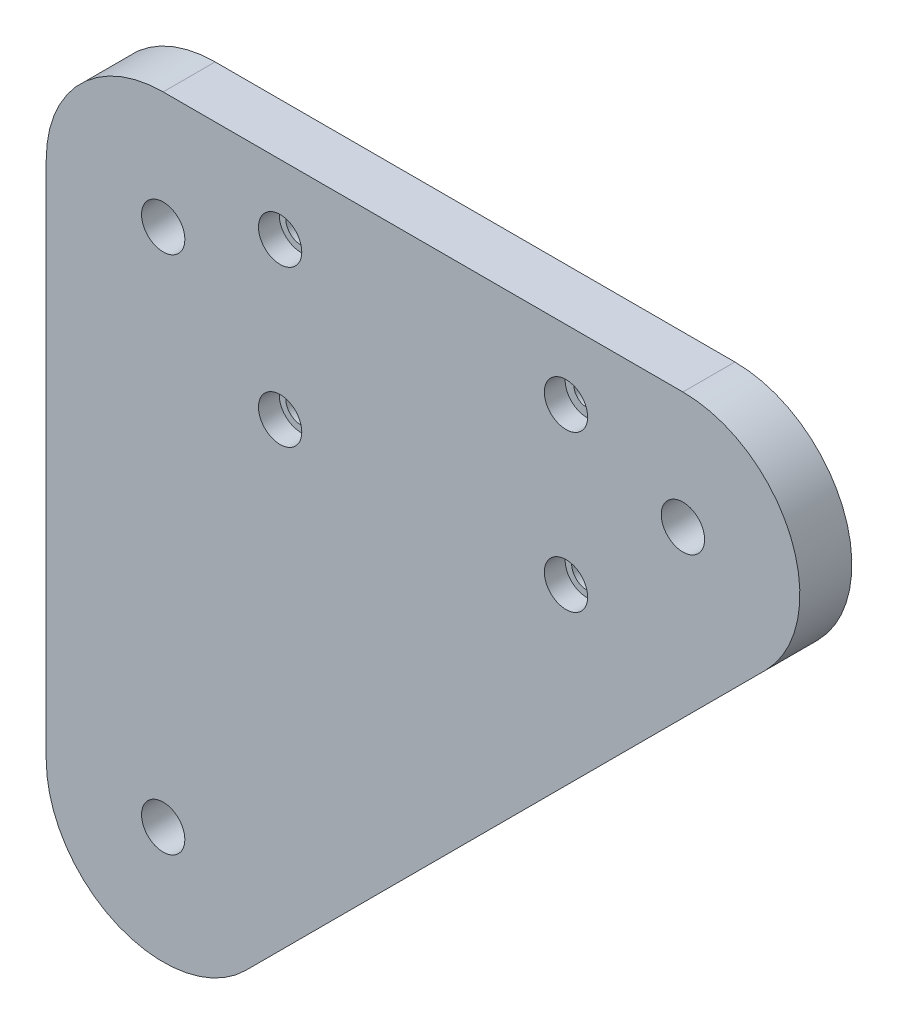
SolidWorks part; units mm, degrees
ref_plane "Plano frontal" through (0, 0, 0) normal (0, 0, 1) x (1, 0, 0)
ref_plane "Plano superior" through (0, 0, 0) normal (0, 1, 0) x (1, 0, 0)
ref_plane "Plano direito" through (0, 0, 0) normal (1, 0, 0) x (0, 0, -1)
sketch "Esboço1" plane through (0, 0, 0) normal (0, 0, 1) x (1, 0, 0)
  line L1 (-30, 30) -> (30, 30) construction
  line L2 (-30, 30) -> (-30, -30) construction
  line L3 (-30, -30) -> (30, -30) construction
  line L4 (30, 30) -> (30, -30) construction
  line L5 (-30, 30) -> (30, -30) construction
  line L6 (-30, -30) -> (30, 30) construction
  line L8 (30, 43.5) -> (-30, 43.5)
  line L23 (-20.4541, -39.5459) -> (39.5459, 20.4541)
  line L26 (-43.5, -30) -> (-43.5, 30)
  circle A0 centre (-30, 30) radius 2.5
  circle A1 centre (-30, -30) radius 2.5
  circle A2 centre (30, 30) radius 2.5
  arc A3 (-30, 43.5) -> (-43.5, 30) centre (-30, 30) ccw
  arc A5 (39.5459, 20.4541) -> (30, 43.5) centre (30, 30) ccw
  circle A7 centre (30, 30) radius 13.5 construction
  arc A8 (-43.5, -30) -> (-20.4541, -39.5459) centre (-30, -30) ccw
  circle A9 centre (-30, 30) radius 13.5 construction
  point P0 (0, 0)
  point P12 (-30, -30)
  point P13 (-20, 22.5)
  point P15 (-20, -22.5)
  point P20 (44, 0)
  point P34 (-81.0386, -15.474)
  point P36 (-81.0386, 15.2242)
  point P37 (-74.2886, -15.474)
  point P43 (-74.2886, 15.2242)
  dimension "D3" = 5
  dimension "D1" = 60
  dimension "D2" = 60
  dimension "D5" = 60
  dimension "D4" = 11
extrude "Ressalto-extrusão1" add sketch "Esboço1" along normal blind 6
ref_axis "Eixo1" through (-30, 30, 6) along (0, 0, -1)
ref_axis "Eixo2" through (30, 30, 6) along (0, 0, -1)
ref_plane "Plano1" through (0, 30, 0) normal (0, 1, 0) x (1, 0, 0)
sketch "Esboço2" plane through (0, 0, 0) normal (0, 0, -1) x (-1, 0, 0)
  circle A0 centre (-16.5, 17.5) radius 1.75 construction
  circle A1 centre (16.5, 17.5) radius 1.75 construction
  circle A2 centre (16.5, 35.5) radius 1.75 construction
  circle A3 centre (-16.5, 35.5) radius 1.5
  circle A9 centre (-16.5, 35.5) radius 1.75 construction
  circle A10 centre (-16.5, 17.5) radius 1.75
  circle A11 centre (16.5, 17.5) radius 1.75
  circle A12 centre (16.5, 35.5) radius 1.75
  circle A13 centre (-16.5, 35.5) radius 1.75 construction
  dimension "D1" = 0.25
extrude "Corte-extrusão1" cut sketch "Esboço2" against normal up to surface (6 mm away) up to face at (-27.5, -30, 6)
sketch "Esboço4" plane through (0, 0, 6) normal (0, 0, 1) x (1, 0, 0)
  circle A0 centre (-16.5, 35.5) radius 2.5
  circle A1 centre (16.5, 35.5) radius 2.5
  circle A2 centre (16.5, 17.5) radius 2.5
  circle A3 centre (-16.5, 17.5) radius 2.5
  dimension "D1" = 5
extrude "Corte-extrusão3" cut sketch "Esboço4" against normal blind 2.4
